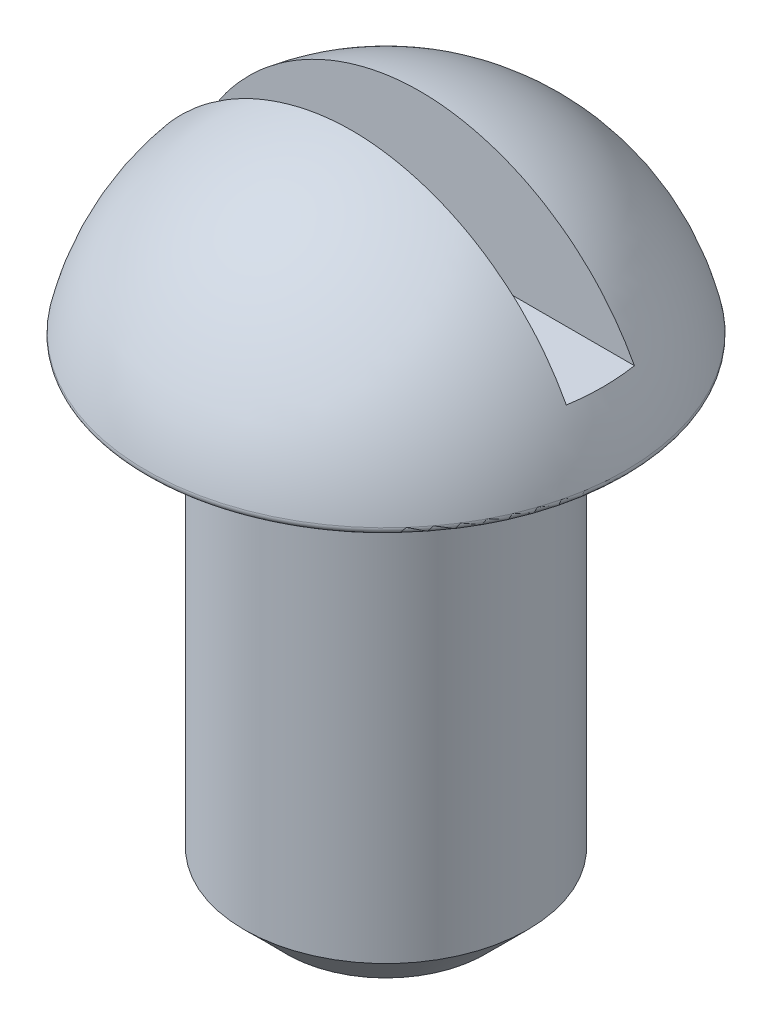
SolidWorks part; units mm, degrees
ref_plane "Спереди" through (0, 0, 0) normal (0, 0, 1) x (1, 0, 0)
ref_plane "Сверху" through (0, 0, 0) normal (0, 1, 0) x (1, 0, 0)
ref_plane "Справа" through (0, 0, 0) normal (1, 0, 0) x (0, 0, -1)
sketch "Эскиз1" plane through (0, 0, 0) normal (0, 0, 1) x (1, 0, 0)
  line L0 (0, 125.7632) -> (0, 0) construction
  line L1 (2.5, 90.7493) -> (4.25, 90.7493)
  line L2 (0, 94.2493) -> (0, 82.2493)
  line L3 (0, 94.2493) -> (0.6, 94.2493)
  line L4 (2.5, 90.7493) -> (2.5, 82.2493)
  line L6 (2.5, 82.2493) -> (0, 82.2493)
  arc A0 (0.6, 94.2493) -> (4.25, 90.7493) centre (-0.0673, 89.9002) cw
  dimension "D1" = 0.6
  dimension "D2" = 3.5
  dimension "D3" = 12
  dimension "D4" = 4.4
  dimension "D5" = 2.5
  dimension "D6" = 4.25
revolve "Повернуть1" add sketch "Эскиз1" angle 360 about L0
ref_axis "Ось4" through (0, 0.56, 0) along (0, -1, 0)
sketch "Эскиз13" plane through (0, 94.2493, 0) normal (0, 1, 0) x (-1, 0, 0)
  line L1 (4.25, -0.6) -> (-4.25, -0.6)
  line L2 (4.25, -0.6) -> (4.25, 0.6)
  line L3 (4.25, 0.6) -> (-4.25, 0.6)
  line L4 (-4.25, -0.6) -> (-4.25, 0.6)
  dimension "D1" = 4.25
  dimension "D2" = 8.5
  dimension "D3" = 0.6
  dimension "D4" = 1.2
extrude "Вырез-Вытянуть9" cut sketch "Эскиз13" against normal blind 2.3
fillet "Скругление1" radius 0.1 1 edges at (-4.25, 90.7493, 0)
chamfer "Фаска1" distance 0.75 angle 45 1 edges at (-2.5, 82.2493, 0)
